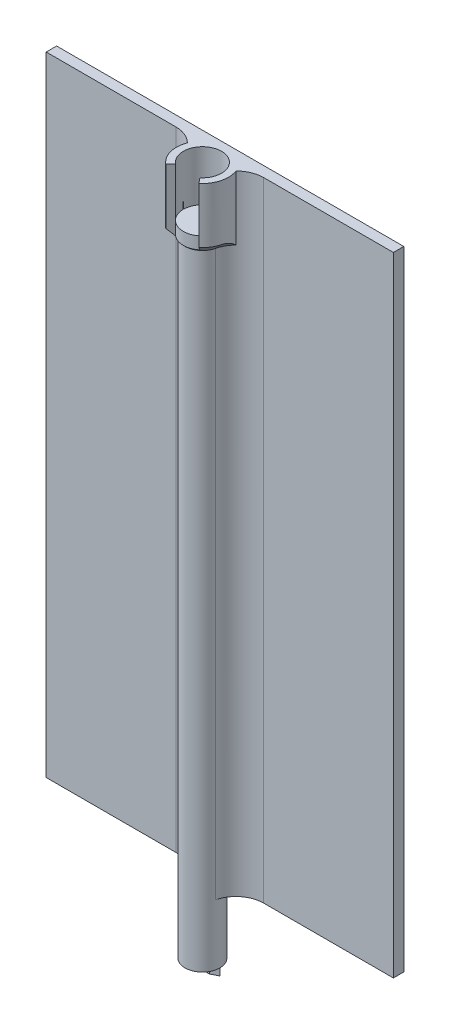
SolidWorks part; units mm, degrees
ref_plane "前视基准面" through (0, 0, 0) normal (0, 0, 1) x (1, 0, 0)
ref_plane "上视基准面" through (0, 0, 0) normal (0, 1, 0) x (1, 0, 0)
ref_plane "右视基准面" through (0, 0, 0) normal (1, 0, 0) x (0, 0, -1)
sketch "草图1" plane through (0, 0, 0) normal (0, 0, 1) x (1, 0, 0)
  line L1 (0, 0) -> (100, 0)
  line L2 (0, 0) -> (0, 170)
  line L3 (0, 170) -> (100, 170)
  line L4 (100, 0) -> (100, 170)
  dimension "D1" = 170
  dimension "D2" = 100
extrude "凸台-拉伸1" add sketch "草图1" along normal blind 3
sketch "草图2" plane through (0, 170, 0) normal (0, 1, 0) x (1, 0, 0)
  line L0 (100, -3) -> (0, -3) construction
  line L1 (45, -8) -> (45, -3)
  line L2 (55, -8) -> (55, -3)
  line L3 (45, -3) -> (55, -3)
  line L4 (100, -3) -> (100, 0) construction
  arc A0 (45, -8) -> (55, -8) centre (50, -8) ccw
  dimension "D1" = 10
  dimension "D2" = 5
  dimension "D3" = 50
extrude "凸台-拉伸2" add sketch "草图2" against normal up to surface (170 mm away) up to face at (50, 0, 1.5)
sketch "草图3" plane through (0, 170, 0) normal (0, 1, 0) x (1, 0, 0)
  circle A0 centre (50, -8) radius 5
extrude "凸台-拉伸3" add sketch "草图3" along normal blind 30
sketch "草图4" plane through (0, 0, 0) normal (0, -1, 0) x (1, 0, 0)
  circle A0 centre (50, 8) radius 5
  dimension "D1" = 10
extrude "凸台-拉伸4" add sketch "草图4" along normal blind 12.5
fillet "圆角1" radius 8 2 edges at (55, 85, 3) (45, 85, 3)
sketch "草图5" plane through (0, -12.5, 0) normal (0, -1, 0) x (1, 0, 0)
  line L0 (47, 9) -> (45, 8)
  line L1 (47, 7) -> (53, 7)
  line L3 (47, 9) -> (53, 9)
  line L7 (45, 8) -> (47, 7)
  line L8 (53, 9) -> (55, 8)
  line L9 (55, 8) -> (53, 7)
  circle A0 centre (50, 8) radius 5 construction
  arc A1 (45.135, 9.1538) -> (54.865, 9.1538) centre (50, 8) ccw construction
  point P0 (50, 8)
  dimension "D1" = 6
  dimension "D2" = 2
extrude "凸台-拉伸5" add sketch "草图5" along normal blind 2
sketch "草图6" plane through (0, 200, 0) normal (0, 1, 0) x (1, 0, 0)
  circle A1 centre (50, -8) radius 5
  circle A2 centre (50, -8) radius 5
  dimension "D1" = 0
extrude "切除-拉伸1" cut sketch "草图6" against normal up to surface (30 mm away) up to face at (50, 170, 2.6811)
sketch "草图7" plane through (0, 170, 0) normal (0, 1, 0) x (1, 0, 0)
  line L5 (62.6491, -3) -> (100, -3)
  line L6 (100, -3) -> (100, 0)
  line L7 (100, 0) -> (0, 0)
  line L8 (0, 0) -> (0, -3)
  line L9 (0, -3) -> (37.3509, -3)
  line L10 (62.6491, -3) -> (100, -3)
  line L11 (100, -3) -> (100, 0)
  line L12 (100, 0) -> (0, 0)
  line L13 (0, 0) -> (0, -3)
  line L14 (0, -3) -> (37.3509, -3)
  arc A0 (42.9922, -5.3277) -> (57.0078, -5.3277) centre (50, -8) ccw
  arc A4 (45.135, -9.1538) -> (37.3509, -3) centre (37.3509, -11) ccw
  arc A5 (45.135, -9.1538) -> (54.865, -9.1538) centre (50, -8) ccw
  arc A6 (62.6491, -3) -> (54.865, -9.1538) centre (62.6491, -11) ccw
  arc A7 (42.9922, -5.3277) -> (37.3509, -3) centre (37.3509, -11) ccw
  arc A9 (62.6491, -3) -> (57.0078, -5.3277) centre (62.6491, -11) ccw
  dimension "D1" = 15
  dimension "D2" = 0
extrude "凸台-拉伸6" add sketch "草图7" along normal blind 16
sketch "草图8" plane through (0, 186, 0) normal (0, 1, 0) x (1, 0, 0)
  circle A0 centre (50, -8) radius 5.5
  dimension "D1" = 11
extrude "切除-拉伸2" cut sketch "草图8" against normal blind 12.5
sketch "草图9" plane through (0, 173.5, 0) normal (0, 1, 0) x (1, 0, 0)
  line L0 (53.0708, -6.7) -> (46.9292, -6.7)
  line L1 (46.9292, -6.7) -> (44.3292, -8)
  line L2 (44.3292, -8) -> (46.9292, -9.3)
  line L3 (46.9292, -9.3) -> (53.0708, -9.3)
  line L4 (53.0708, -9.3) -> (55.6708, -8)
  line L5 (55.6708, -8) -> (53.0708, -6.7)
extrude "切除-拉伸3" cut sketch "草图9" against normal blind 2
sketch "草图10" plane through (0, 186, 0) normal (0, 1, 0) x (1, 0, 0)
  line L0 (45.2273, -13.7854) -> (46.5, -12.2426)
  line L1 (53.5, -12.2426) -> (54.7727, -13.7854)
  line L7 (62.6491, -3) -> (100, -3)
  line L8 (100, -3) -> (100, 0)
  line L9 (100, 0) -> (0, 0)
  line L10 (0, 0) -> (0, -3)
  line L11 (0, -3) -> (37.3509, -3)
  arc A2 (42.9922, -5.3277) -> (57.0078, -5.3277) centre (50, -8) ccw construction
  circle A3 centre (50, -8) radius 5.5 construction
  arc A4 (46.5, -12.2426) -> (53.5, -12.2426) centre (50, -8) ccw
  arc A6 (42.9922, -5.3277) -> (37.3509, -3) centre (37.3509, -11) ccw
  arc A7 (42.9922, -5.3277) -> (57.0078, -5.3277) centre (50, -8) ccw
  arc A8 (62.6491, -3) -> (57.0078, -5.3277) centre (62.6491, -11) ccw
  arc A10 (45.2273, -13.7854) -> (54.7727, -13.7854) centre (50, -8) ccw
  dimension "D1" = 3.5
  dimension "D2" = 3.5
  dimension "D3" = 0
extrude "切除-拉伸4" cut sketch "草图10" against normal up to next
chamfer "倒角2" distance 2.5 angle 45 3 edges at (44.3309, 170, 7.0911) (55.6691, 170, 7.0911) (50, 170, 13)
sketch "草图11" plane through (0, 173.5, 0) normal (0, 1, 0) x (1, 0, 0)
  line L0 (46.9292, -9.3) -> (44.5007, -8.0857) construction
  line L1 (55.4993, -8.0857) -> (53.0708, -9.3) construction
  line L2 (53.0708, -9.3) -> (46.9292, -9.3) construction
  line L3 (53.0708, -6.7) -> (55.4993, -7.9143) construction
  line L4 (44.5007, -7.9143) -> (46.9292, -6.7) construction
  line L5 (46.9292, -6.7) -> (53.0708, -6.7) construction
  line L6 (46.9292, -9.3) -> (44.5007, -8.0857)
  line L7 (55.4993, -8.0857) -> (53.0708, -9.3)
  line L8 (53.0708, -9.3) -> (46.9292, -9.3)
  line L9 (53.0708, -6.7) -> (55.4993, -7.9143)
  line L10 (44.5007, -7.9143) -> (46.9292, -6.7)
  line L11 (46.9292, -6.7) -> (53.0708, -6.7)
  arc A0 (44.5007, -8.0857) -> (46.5, -12.2426) centre (50, -8) ccw construction
  arc A1 (46.5, -12.2426) -> (53.5, -12.2426) centre (50, -8) ccw construction
  arc A2 (53.5, -12.2426) -> (55.4993, -8.0857) centre (50, -8) ccw construction
  arc A3 (55.4993, -7.9143) -> (44.5007, -7.9143) centre (50, -8) ccw construction
  arc A4 (44.5007, -8.0857) -> (46.5, -12.2426) centre (50, -8) ccw
  arc A5 (46.5, -12.2426) -> (53.5, -12.2426) centre (50, -8) ccw
  arc A6 (53.5, -12.2426) -> (55.4993, -8.0857) centre (50, -8) ccw
  arc A7 (55.4993, -7.9143) -> (44.5007, -7.9143) centre (50, -8) ccw
extrude "切除-拉伸5" cut sketch "草图11" against normal blind 2
sketch "草图12" plane through (0, 0, 0) normal (0, -1, 0) x (1, 0, 0)
  line L5 (37.3509, 3) -> (0, 3)
  line L6 (0, 3) -> (0, 0)
  line L7 (0, 0) -> (100, 0)
  line L8 (100, 0) -> (100, 3)
  line L9 (100, 3) -> (62.6491, 3)
  line L10 (37.3509, 3) -> (0, 3)
  line L11 (0, 3) -> (0, 0)
  line L12 (0, 0) -> (100, 0)
  line L13 (100, 0) -> (100, 3)
  line L14 (100, 3) -> (62.6491, 3)
  arc A3 (45.135, 9.1538) -> (54.865, 9.1538) centre (50, 8) ccw
  arc A4 (37.3509, 3) -> (45.135, 9.1538) centre (37.3509, 11) ccw
  arc A5 (54.865, 9.1538) -> (62.6491, 3) centre (62.6491, 11) ccw
  arc A6 (45.135, 9.1538) -> (54.865, 9.1538) centre (50, 8) ccw
  arc A7 (37.3509, 3) -> (45.135, 9.1538) centre (37.3509, 11) ccw
  arc A8 (54.865, 9.1538) -> (62.6491, 3) centre (62.6491, 11) ccw
  dimension "D1" = 0
extrude "切除-拉伸6" cut sketch "草图12" against normal blind 5
